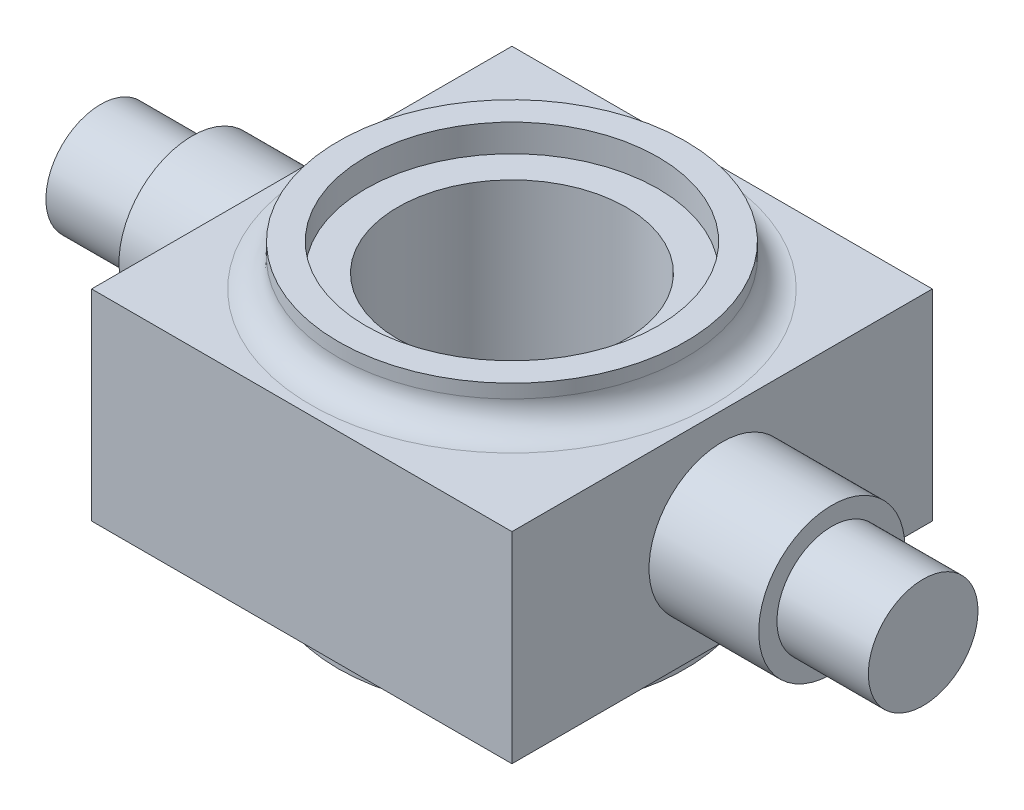
SolidWorks part; units mm, degrees
material "Plain Carbon Steel"
ref_plane "Front Plane" through (0, 0, 0) normal (0, 0, 1) x (1, 0, 0)
ref_plane "Top Plane" through (0, 0, 0) normal (0, 1, 0) x (1, 0, 0)
ref_plane "Right Plane" through (0, 0, 0) normal (1, 0, 0) x (0, 0, -1)
sketch "Sketch1" plane through (0, 0, 0) normal (0, 1, 0) x (1, 0, 0)
  line L1 (23, 23) -> (-23, 23)
  line L2 (23, 23) -> (23, -23)
  line L3 (23, -23) -> (-23, -23)
  line L4 (-23, 23) -> (-23, -23)
  line L5 (23, 23) -> (-23, -23) construction
  line L6 (23, -23) -> (-23, 23) construction
  point P0 (0, 0)
  dimension "D1" = 46
  dimension "D2" = 46
extrude "Boss-Extrude1" add sketch "Sketch1" along normal mid plane 22
sketch "Sketch3" plane through (0, 11, 0) normal (0, 1, 0) x (1, 0, 0)
  circle A0 centre (0, 0) radius 19
  dimension "D1" = 38
extrude "Boss-Extrude3" add sketch "Sketch3" along normal blind 4.5
mirror "Mirror1" about plane through (0, 0, 0) normal (0, 1, 0) of "Boss-Extrude3"
sketch "Sketch4" plane through (0, 15.5, 0) normal (0, 1, 0) x (1, 0, 0)
  circle A0 centre (0, 0) radius 16
  dimension "D1" = 32
extrude "Cut-Extrude1" cut sketch "Sketch4" against normal blind 3 and the other way through all
mirror "Mirror2" about plane through (0, 0, 0) normal (0, 1, 0) of "Cut-Extrude1"
sketch "Sketch5" plane through (0, 12.5, 0) normal (0, 1, 0) x (1, 0, 0)
  circle A0 centre (0, 0) radius 12.5
  dimension "D1" = 25
extrude "Cut-Extrude2" cut sketch "Sketch5" against normal through all
sketch "Sketch6" plane through (23, 0, 0) normal (1, 0, 0) x (0, 0, -1)
  circle A0 centre (0, 0) radius 8
  circle A1 centre (0, 0) radius 6
  dimension "D1" = 16
  dimension "D2" = 12
extrude "Boss-Extrude4" add sketch "Sketch6" along normal blind 12 contours A0
extrude "Boss-Extrude5" add sketch "Sketch6<3>" along normal blind 22 contours A1
sketch "Sketch6<3>" plane through (23, 0, 0) normal (1, 0, 0) x (0, 0, -1) same geometry as "Sketch6"
cosmetic thread "Cosmetic Thread1" parameters "D1"=8, "D2"=10.072
mirror "Mirror3" about plane through (0, 0, 0) normal (1, 0, 0) of "Boss-Extrude5", "Boss-Extrude4"
cosmetic thread "Cosmetic Thread2" parameters "D1"=8, "D2"=10.072
fillet "Fillet1" radius 3 2 edges at (0, -11, 19) (0, 11, 19)
